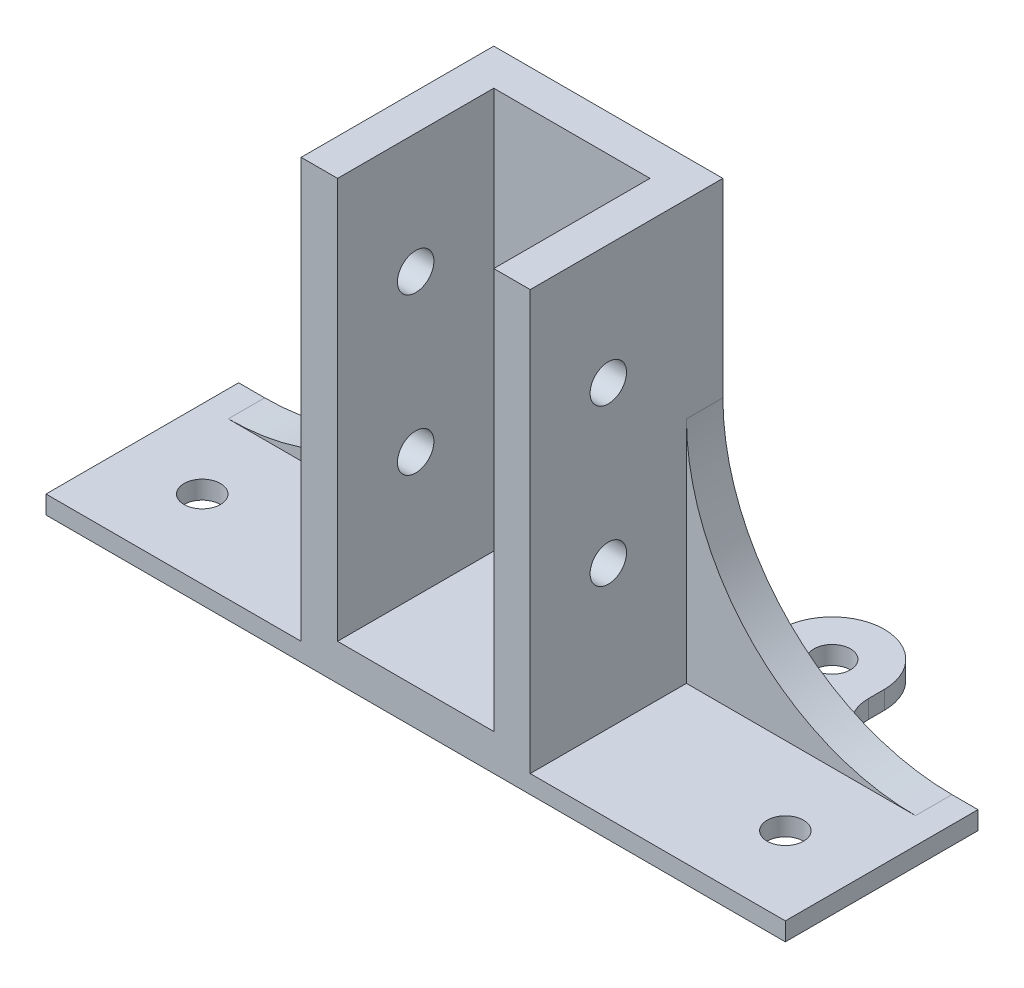
SolidWorks part; units mm, degrees
ref_plane "Front Plane" through (0, 0, 0) normal (0, 0, 1) x (1, 0, 0)
ref_plane "Top Plane" through (0, 0, 0) normal (0, 1, 0) x (1, 0, 0)
ref_plane "Right Plane" through (0, 0, 0) normal (1, 0, 0) x (0, 0, -1)
sketch "Sketch1" plane through (0, 0, 0) normal (0, 0, 1) x (1, 0, 0)
  line L1 (-16.1393, 44.8689) -> (5.8607, 44.8689)
  line L2 (-16.1393, 44.8689) -> (-16.1393, 2.8689)
  line L3 (-16.1393, 2.8689) -> (5.8607, 2.8689)
  line L4 (5.8607, 44.8689) -> (5.8607, 2.8689)
  dimension "D1" = 22
  dimension "D2" = 42
extrude "Boss-Extrude1" add sketch "Sketch1" along normal blind 18.5
sketch "Sketch2" plane through (0, 0, 18.5) normal (0, 0, 1) x (1, 0, 0)
  line L0 (5.8607, 44.8689) -> (-16.1393, 44.8689) construction
  line L1 (-12.6393, 44.8689) -> (2.3607, 44.8689)
  line L2 (-12.6393, 44.8689) -> (-12.6393, 6.3689)
  line L3 (-12.6393, 6.3689) -> (2.3607, 6.3689)
  line L4 (2.3607, 44.8689) -> (2.3607, 6.3689)
  line L5 (5.8607, 2.8689) -> (5.8607, 44.8689) construction
  line L6 (-16.1393, 2.8689) -> (5.8607, 2.8689) construction
  dimension "D1" = 15
  dimension "D2" = 3.5
  dimension "D3" = 3.5
extrude "Cut-Extrude1" cut sketch "Sketch2" against normal blind 15
sketch "Sketch3" plane through (0, 0, 0) normal (0, 0, -1) x (-1, 0, 0)
  line L1 (16.1393, 2.8689) -> (40.6393, 2.8689)
  line L2 (16.1393, 2.8689) -> (16.1393, 4.6189)
  line L3 (16.1393, 4.6189) -> (40.6393, 4.6189)
  line L4 (40.6393, 2.8689) -> (40.6393, 4.6189)
  line L5 (-5.8607, 2.8689) -> (-30.3607, 2.8689)
  line L6 (-5.8607, 2.8689) -> (-5.8607, 4.6189)
  line L7 (-5.8607, 4.6189) -> (-30.3607, 4.6189)
  line L8 (-30.3607, 2.8689) -> (-30.3607, 4.6189)
  dimension "D1" = 24.5
  dimension "D2" = 24.5
  dimension "D3" = 1.75
  dimension "D4" = 1.75
extrude "Boss-Extrude2" add sketch "Sketch3" against normal up to surface (18.5 mm away) up to face at (-5.1393, 24.7439, 18.5)
sketch "Sketch4" plane through (0, 0, 0) normal (0, 0, -1) x (-1, 0, 0)
  line L0 (38.1393, 4.6189) -> (16.1393, 4.6189)
  line L1 (40.6393, 4.6189) -> (16.1393, 4.6189) construction
  line L2 (16.1393, 4.6189) -> (16.1393, 26.6189)
  line L3 (16.1393, 44.8689) -> (16.1393, 4.6189) construction
  line L4 (-27.8607, 4.6189) -> (-5.8607, 4.6189)
  line L5 (-5.8607, 4.6189) -> (-30.3607, 4.6189) construction
  line L6 (-5.8607, 4.6189) -> (-5.8607, 26.6189)
  line L7 (-5.8607, 4.6189) -> (-5.8607, 44.8689) construction
  arc A0 (16.1393, 26.6189) -> (38.1393, 4.6189) centre (38.1393, 26.6189) ccw
  arc A1 (-5.8607, 26.6189) -> (-27.8607, 4.6189) centre (-27.8607, 26.6189) cw
  dimension "D1" = 22
extrude "Boss-Extrude3" add sketch "Sketch4" against normal blind 3.5
sketch "Sketch5" plane through (0, 2.8689, 0) normal (0, -1, 0) x (1, 0, 0)
  line L0 (-40.6393, 0) -> (30.3607, 0) construction
  line L1 (5.8607, 0) -> (-16.1393, 0) construction
  line L2 (15.8607, -5.5) -> (15.8607, 0)
  line L3 (-26.1393, -5.5) -> (-26.1393, 0)
  line L4 (-16.1393, -5.5) -> (-16.1393, 0)
  line L5 (5.8607, -5.5) -> (5.8607, 0)
  line L6 (15.8607, 0) -> (5.8607, 0)
  line L7 (-16.1393, 0) -> (-26.1393, 0)
  circle A0 centre (10.8607, -5.5) radius 1.75
  circle A1 centre (-21.1393, -5.5) radius 1.75
  arc A2 (5.8607, -5.5) -> (15.8607, -5.5) centre (10.8607, -5.5) ccw
  arc A3 (-26.1393, -5.5) -> (-16.1393, -5.5) centre (-21.1393, -5.5) ccw
  point P6 (-5.1393, 0)
  point P7 (-5.1393, 0)
  dimension "D4" = 3.5
  dimension "D1" = 5.5
  dimension "D2" = 16
  dimension "D3" = 16
extrude "Boss-Extrude4" add sketch "Sketch5" against normal up to surface (1.75 mm away) up to face at (-33.8893, 4.6189, 8.5833)
sketch "Sketch6" plane through (0, 4.6189, 0) normal (0, 1, 0) x (1, 0, 0)
  line L0 (30.3607, -11) -> (-40.6393, -11) construction
  line L1 (30.3607, -18.5) -> (30.3607, 0) construction
  line L2 (-40.6393, -18.5) -> (-40.6393, 0) construction
  line L3 (5.8607, -18.5) -> (30.3607, -18.5) construction
  circle A0 centre (22.8607, -11) radius 1.75
  circle A1 centre (-33.1393, -11) radius 1.75
  dimension "D2" = 7.5
  dimension "D3" = 7.5
  dimension "D4" = 3.5
  dimension "D1" = 7.5
extrude "Cut-Extrude2" cut sketch "Sketch6" against normal blind 10
fillet "Fillet1" radius 4 4 edges at (-26.1393, 3.7439, 0) (-16.1393, 3.7439, 0)
sketch "Sketch7" plane through (-16.1393, 0, 0) normal (-1, 0, 0) x (0, 0, 1)
  line L0 (11, 44.8689) -> (11, 4.6189) construction
  line L1 (18.5, 44.8689) -> (0, 44.8689) construction
  line L2 (18.5, 4.6189) -> (0, 4.6189) construction
  line L3 (18.5, 44.8689) -> (18.5, 4.6189) construction
  line L4 (3.5, 6.3689) -> (18.5, 6.3689) construction
  circle A0 centre (11, 33.3689) radius 1.75
  circle A1 centre (11, 18.3689) radius 1.75
  dimension "D2" = 3.5
  dimension "D1" = 7.5
  dimension "D3" = 15
  dimension "D4" = 12
extrude "Cut-Extrude3" cut sketch "Sketch7" against normal blind 28
sketch "Sketch8" plane through (0, 0, 0) normal (0, 0, -1) x (-1, 0, 0)
  line L0 (5.1393, 44.8689) -> (5.1393, 2.8689) construction
  line L1 (-5.8607, 44.8689) -> (16.1393, 44.8689) construction
  line L2 (12.1393, 2.8689) -> (-1.8607, 2.8689) construction
  line L3 (12.6393, 6.3689) -> (-2.3607, 6.3689) construction
  circle A0 centre (5.1393, 33.3689) radius 1.75
  circle A1 centre (5.1393, 18.3689) radius 1.75
  dimension "D1" = 15
  dimension "D2" = 12
  dimension "D3" = 3.5
extrude "Cut-Extrude4" cut sketch "Sketch8" against normal blind 28
